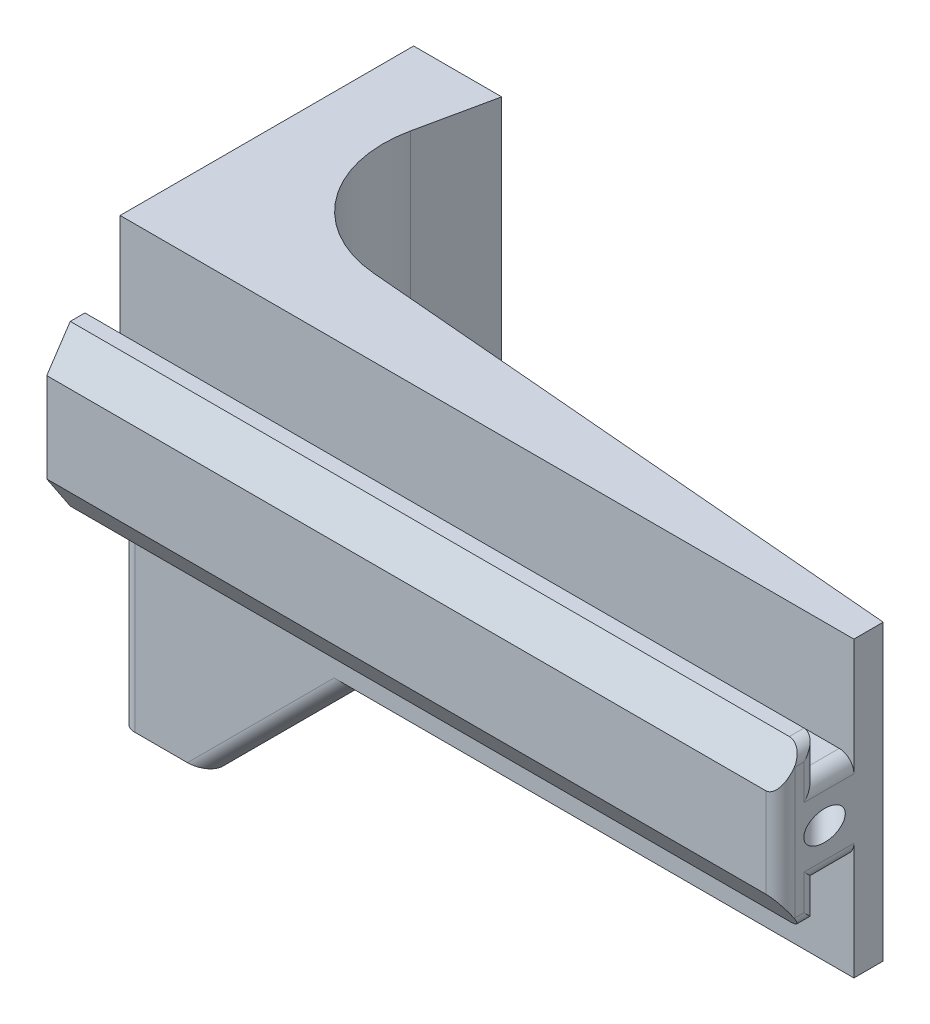
SolidWorks part; units mm, degrees
ref_plane "Front Plane" through (0, 0, 0) normal (0, 0, 1) x (1, 0, 0)
ref_plane "Top Plane" through (0, 0, 0) normal (0, 1, 0) x (1, 0, 0)
ref_plane "Right Plane" through (0, 0, 0) normal (1, 0, 0) x (0, 0, -1)
sketch "Sketch1" plane through (0, 0, 0) normal (0, 1, 0) x (1, 0, 0)
  line L1 (-25, 12.5) -> (25, 12.5)
  line L2 (-25, 12.5) -> (-25, -12.5)
  line L3 (-25, -12.5) -> (25, -12.5)
  line L4 (25, 12.5) -> (25, -12.5)
  line L5 (-25, 12.5) -> (25, -12.5) construction
  line L6 (-25, -12.5) -> (25, 12.5) construction
  point P0 (0, 0)
  dimension "D1" = 50
  dimension "D2" = 25
extrude "Boss-Extrude1" add sketch "Sketch1" along normal blind 20
sketch "Sketch2" plane through (25, 0, 0) normal (1, 0, 0) x (0, 0, -1)
  line L0 (-12.5, 10) -> (-7.5, 10) construction
  line L1 (-12.5, 20) -> (-12.5, 0) construction
  line L2 (-7.5, 13.05) -> (-7.5, 6.95) construction
  line L3 (-7.5, 13.05) -> (-9.9, 13.05)
  line L4 (-7.5, 6.95) -> (-9.9, 6.95)
  line L5 (-9.9, 13.05) -> (-9.9, 15.45)
  line L6 (-9.9, 15.45) -> (-10.9, 15.45)
  line L7 (-9.9, 6.95) -> (-9.9, 4.55)
  line L8 (-9.9, 4.55) -> (-10.9, 4.55)
  line L9 (-7.5, 13.05) -> (-7.5, 20)
  line L10 (-12.5, 20) -> (12.5, 20) construction
  line L11 (-7.5, 6.95) -> (-7.5, 0)
  line L12 (-12.5, 0) -> (12.5, 0) construction
  line L13 (-9.9, 13.05) -> (-12.5, 13.05) construction
  line L14 (-10.9, 15.45) -> (-12.5, 13.05)
  line L15 (-9.9, 6.95) -> (-12.5, 6.95) construction
  line L16 (-10.9, 4.55) -> (-12.5, 6.95)
  line L17 (-12.5, 6.95) -> (-12.5, 13.05)
  point P7 (-7.5, 10)
  point P8 (-12.5, 10)
  dimension "D1" = 5
  dimension "D2" = 6.1
  dimension "D3" = 2.4
  dimension "D4" = 2.4
  dimension "D5" = 1
extrude "Cut-Extrude1" cut sketch "Sketch2" along direction (-1, 0, 0) on the side against the normal through all and the other way through all
sketch "Sketch4" plane through (0, 0, 0) normal (0, -1, 0) x (-1, 0, 0)
  line L0 (-25, -7.5) -> (-25, -5.5) construction
  line L1 (-25, -7.5) -> (-25, 12.5) construction
  line L2 (25, 12.5) -> (19, 12.5) construction
  line L3 (-25, 12.5) -> (25, 12.5) construction
  line L4 (25, -1.5) -> (22, -1.5) construction
  line L6 (19, 12.5) -> (20.0977, 7.3775)
  line L7 (12.9537, -2.2699) -> (-25, -5.5)
  line L8 (22, -1.5) -> (22, -7.5) construction
  line L9 (25, -7.5) -> (-25, -7.5) construction
  arc A0 (12.9537, -2.2699) -> (20.0977, 7.3775) centre (12.2753, 5.7013) ccw
  point P17 (0, 0)
  point P18 (0, 0)
  point P22 (0, 0)
  dimension "D4" = 8
  dimension "D1" = 2
  dimension "D2" = 3
  dimension "D3" = 6
  dimension "D5" = 6
extrude "Cut-Extrude2" cut sketch "Sketch4" against normal through all and the other way through all flip side to cut
sketch "Sketch6" plane through (25, 0, 0) normal (1, 0, 0) x (0, 0, -1)
  line L0 (-5.5, 10) -> (-9.5, 10) construction
  line L1 (-5.5, 0) -> (-5.5, 20) construction
  point P4 (0, 0)
  dimension "D1" = 4
sketch "Sketch7" plane through (0, 0, 0) normal (0, 1, 0) x (1, 0, 0)
  line L0 (25, -9.5) -> (19.88, -4.38)
  line L1 (25, -5.5) -> (25, -9.5) construction
ref_plane "Plane1" through (25, 10, 9.5) normal (-0.7071, 0, -0.7071) x (-0.7071, 0, 0.7071)
sketch "Sketch12" plane through (25, 10, 9.5) normal (-0.7071, 0, -0.7071) x (-0.7071, 0, 0.7071)
  circle A0 centre (0, 0) radius 1
  dimension "D1" = 2
extrude "Cut-Extrude3" cut sketch "Sketch12" along normal mid plane 20
fillet "Fillet2" radius 1 7 edges at (25, 10, 12.5) (25, 13.05, 8.7) (25, 14.25, 9.9) (25, 15.45, 10.4) (25, 4.55, 10.4) (25, 5.75, 9.9) (25, 6.95, 8.7)
sketch "Sketch13" plane through (0, 0, 0) normal (0, -1, 0) x (1, 0, 0)
  line L1 (-25, 7.5) -> (-19, 7.5)
  line L2 (-25, 7.5) -> (-25, 1.5)
  line L3 (-25, 1.5) -> (-19, 1.5)
  line L4 (-19, 7.5) -> (-19, 1.5)
  dimension "D1" = 6
extrude "Boss-Extrude2" add sketch "Sketch13" along normal blind 10
ref_plane "Plane2" through (-19, 0, 1.5) normal (0, 0, 1) x (1, 0, 0)
chamfer "Chamfer1" distance 10 angle 45 1 edges at (-19, 0, 4.5)
fillet "Fillet4" radius 1 2 edges at (-14, -5, 7.5) (-25, -1.525, 7.5)
